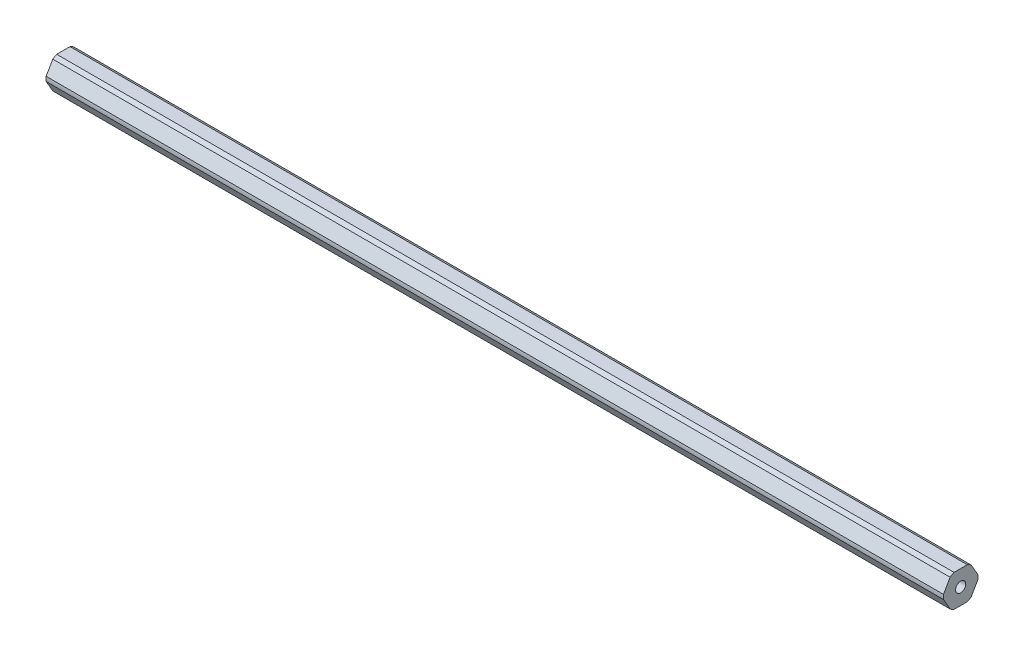
SolidWorks part; units mm, degrees
material "7075-T6 (SN)"
ref_plane "Front Plane" through (0, 0, 0) normal (0, 0, 1) x (1, 0, 0)
ref_plane "Top Plane" through (0, 0, 0) normal (0, 1, 0) x (1, 0, 0)
ref_plane "Right Plane" through (0, 0, 0) normal (1, 0, 0) x (0, 0, -1)
sketch "Sketch1" plane through (0, 0, 0) normal (1, 0, 0) x (0, 0, -1)
  line L1 (3.6662, 6.35) -> (-3.6662, 6.35)
  line L2 (-3.6662, 6.35) -> (-7.3323, 0)
  line L3 (-7.3323, 0) -> (-3.6662, -6.35)
  line L4 (-3.6662, -6.35) -> (3.6662, -6.35)
  line L5 (3.6662, -6.35) -> (7.3323, 0)
  line L6 (7.3323, 0) -> (3.6662, 6.35)
  circle A0 centre (0, 0) radius 6.875
  circle A1 centre (0, 0) radius 2.0193
  circle A2 centre (0, 0) radius 6.35 construction
  point P4 (0, 0)
  point P12 (3.1415, 5.4548)
  dimension "D1" = 12.7
  dimension "D2" = 13.75
  dimension "D3" = 4.0386
extrude "Boss-Extrude1" add sketch "Sketch1" along normal mid plane 355.6 contours L6 A0 L1 L2 L3 L4 L5 A1 region at (0, 5.7918, -3.3439)
hole_wizard "#10-32 Tapped Hole1" positions "3DSketch1" profile "Sketch2" tap size "#10-32" standard "ANSI Inch"
sketch3d "3DSketch1"
  circle A0 centre (-177.8, 0, 0) radius 2.0193 construction
  circle A1 centre (177.8, 0, 0) radius 2.0193 construction
  point P0 (177.8, 0, 0)
  point P2 (-177.8, 0, 0)
  point P7 (-175.7807, 0, 0)
  point P10 (179.8193, 0, 0)
sketch "Sketch2" plane through (177.8, 0, 0) normal (0, 1, 0) x (0, 0, -1)
  line L0 (0, 0) -> (0, 17.5608)
  line L1 (0, 17.5608) -> (2.0193, 16.3474)
  line L2 (2.0193, 16.3474) -> (2.0193, 0)
  line L5 (2.0193, 0) -> (0, 0)
  line L10 (0, 17.5608) -> (-2.0193, 16.3474) construction
  line L11 (0, -6.35) -> (0, 107.95) construction
  dimension "Tap Drill Dia." = 4.0386
  dimension "Tap Drill Depth" = 16.3474
  dimension "Drill Angle" = 118
cosmetic thread "Hole Thread1" parameters "D1"=13.97, "D2"=4.826
cosmetic thread "Hole Thread2" parameters "D1"=13.97, "D2"=4.826
equation "\"D2@Sketch1\"=13.75mm"
